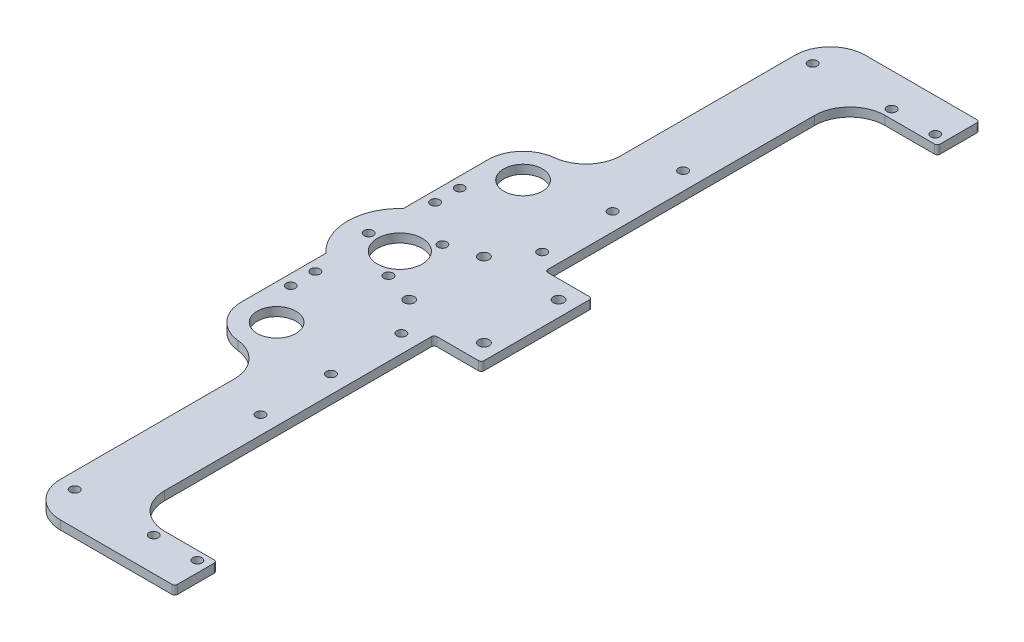
SolidWorks part; units mm, degrees
ref_plane "Front Plane" through (0, 0, 0) normal (0, 0, 1) x (1, 0, 0)
ref_plane "Top Plane" through (0, 0, 0) normal (0, 1, 0) x (1, 0, 0)
ref_plane "Right Plane" through (0, 0, 0) normal (1, 0, 0) x (0, 0, -1)
sketch "Sketch1" plane through (0, 0, 0) normal (0, 1, 0) x (1, 0, 0)
  line L0 (-67.9713, -52.7283) -> (-67.9713, -82.5864)
  line L6 (-67.9713, 4.9919) -> (-67.9713, -24.8662)
  line L17 (8.6823, 106.3552) -> (-32.5284, 106.3552)
  line L20 (-32.5284, -183.9497) -> (7.3984, -183.9497)
  line L24 (-10.2035, 91.1152) -> (8.6823, 91.1152)
  line L26 (7.3984, -183.9497) -> (8.6823, -183.9497)
  line L28 (-10.2035, -168.7097) -> (8.6823, -168.7097)
  line L30 (8.6823, -168.7097) -> (8.6823, -183.9497)
  line L31 (-45.2284, -108.5097) -> (-45.2284, -171.2497)
  line L32 (8.6823, 106.3552) -> (8.6823, 91.1152)
  line L33 (-45.2284, 93.6552) -> (-45.2284, 30.9152)
  line L34 (-22.9035, -156.0097) -> (-22.9035, -58.7973)
  line L35 (-22.9035, -38.7973) -> (-5.9035, -38.7973) construction
  line L40 (-5.9035, -38.7973) -> (-5.9035, -18.7973)
  line L41 (-5.9035, -38.7973) -> (-5.9035, -58.7973)
  line L42 (-5.9035, -18.7973) -> (-22.9035, -18.7973)
  line L43 (-5.9035, -58.7973) -> (-22.9035, -58.7973)
  line L44 (-22.9035, -18.7973) -> (-22.9035, 78.4152)
  arc A0 (-67.9713, -82.5864) -> (-56.6084, -95.8785) centre (-55.2885, -83.2473) ccw
  arc A1 (-45.2284, -108.5097) -> (-56.6084, -95.8785) centre (-57.9284, -108.5097) ccw
  arc A4 (-56.6084, 18.284) -> (-45.2284, 30.9152) centre (-57.9284, 30.9152) ccw
  arc A5 (-56.6084, 18.284) -> (-67.9713, 4.9919) centre (-55.2885, 5.6527) ccw
  arc A6 (-67.9713, -24.8662) -> (-67.9713, -52.7283) centre (-55.2885, -38.7973) ccw
  arc A22 (-45.2284, 93.6552) -> (-32.5284, 106.3552) centre (-32.5284, 93.6552) cw
  arc A23 (-45.2284, -171.2497) -> (-32.5284, -183.9497) centre (-32.5284, -171.2497) ccw
  arc A24 (-22.9035, 78.4152) -> (-10.2035, 91.1152) centre (-10.2035, 78.4152) cw
  arc A25 (-22.9035, -156.0097) -> (-10.2035, -168.7097) centre (-10.2035, -156.0097) ccw
  circle A30 centre (-55.2885, -83.2473) radius 6.985 construction
  circle A31 centre (-64.1613, -69.2773) radius 1.65 construction
  circle A32 centre (-64.1613, -60.3873) radius 1.65 construction
  circle A33 centre (-55.2885, -38.7973) radius 8.0645 construction
  circle A34 centre (-49.6688, -29.0636) radius 1.65 construction
  circle A35 centre (-49.6688, -48.531) radius 1.65 construction
  circle A36 centre (-66.528, -38.7973) radius 1.65 construction
  circle A37 centre (-64.1613, -17.2073) radius 1.65 construction
  circle A38 centre (-64.1613, -8.3173) radius 1.65 construction
  circle A39 centre (-55.2885, 5.6527) radius 6.985 construction
  circle A40 centre (-55.2885, -83.2473) radius 6.985
  circle A41 centre (-64.1613, -69.2773) radius 1.65
  circle A42 centre (-64.1613, -60.3873) radius 1.65
  circle A43 centre (-55.2885, -38.7973) radius 8.0645
  circle A44 centre (-49.6688, -29.0636) radius 1.65
  circle A45 centre (-49.6688, -48.531) radius 1.65
  circle A46 centre (-66.528, -38.7973) radius 1.65
  circle A47 centre (-64.1613, -17.2073) radius 1.65
  circle A48 centre (-64.1613, -8.3173) radius 1.65
  circle A49 centre (-55.2885, 5.6527) radius 6.985
  circle A50 centre (-29.342, 37.4027) radius 1.65 construction
  circle A51 centre (-29.342, 12.0027) radius 1.65 construction
  circle A52 centre (-29.342, -13.3973) radius 1.65 construction
  circle A54 centre (-29.342, -64.1973) radius 1.65 construction
  circle A55 centre (-29.342, -89.5973) radius 1.65 construction
  circle A56 centre (-29.342, -114.9973) radius 1.65 construction
  circle A57 centre (-29.342, 37.4027) radius 1.65
  circle A58 centre (-29.342, 12.0027) radius 1.65
  circle A59 centre (-29.342, -13.3973) radius 1.65
  circle A61 centre (-29.342, -64.1973) radius 1.65
  circle A62 centre (-29.342, -89.5973) radius 1.65
  circle A63 centre (-29.342, -114.9973) radius 1.65
  point P58 (-45.2284, 106.3552)
  dimension "D3" = 63.9708
  dimension "D5" = 15.24
  dimension "D6" = 10.0601
  dimension "D7" = 32.385
  dimension "D8" = 62.74
  dimension "D44" = 12.7
  dimension "D46" = 12.7
  dimension "D47" = 12.7
  dimension "D1" = 17
  dimension "D2" = 20
extrude "Boss-Extrude1" add sketch "Sketch1" along normal blind 3.175 contours A25 A24 L24 L32 A22 A4 A5 L6 A6 L0 A0 A1 A23 L20 L26 L30 L28 A63 A62 A61 A59 A58 A57 A49 A48 A47 A46 region at (-34.9114, 0, 38.7973)
sketch "Sketch4" plane through (0, 3.175, 0) normal (0, 1, 0) x (1, 0, 0)
  circle A0 centre (4.754, 94.2902) radius 1.65
  circle A1 centre (-10.971, 94.2902) radius 1.65
  circle A2 centre (-39.471, 94.2902) radius 1.65
  circle A3 centre (-39.471, -171.8847) radius 1.65
  circle A4 centre (-10.971, -171.8847) radius 1.65
  circle A5 centre (4.754, -171.8847) radius 1.65
  dimension "D1" = 3.3
extrude "Cut-Extrude1" cut sketch "Sketch4" against normal through all
sketch "Sketch5" plane through (0, 3.175, 0) normal (0, 1, 0) x (1, 0, 0)
  circle A1 centre (-11.5006, -25.3269) radius 1.8986
  circle A2 centre (-38.4414, -25.3269) radius 1.8986
  circle A5 centre (-38.4414, -52.2677) radius 1.8986
  circle A6 centre (-11.5006, -52.2677) radius 1.8986
  point P9 (-38.4414, -52.2677)
  point P17 (-11.5006, -52.2677)
  point P18 (-11.5006, -25.3269)
  point P19 (-38.4414, -52.2677)
  dimension "D1" = 3.7973
extrude "Cut-Extrude2" cut sketch "Sketch5" against normal through all
fillet "Fillet1" radius 1 8 edges at (-22.9035, 1.5875, 18.7973) (-22.9035, 1.5875, 58.7973) (8.6823, 1.5875, 183.9497) (8.6823, 1.5875, 168.7097) (-5.9035, 1.5875, 58.7973) (-5.9035, 1.5875, 18.7973) (8.6823, 1.5875, -106.3552) (8.6823, 1.5875, -91.1152)
